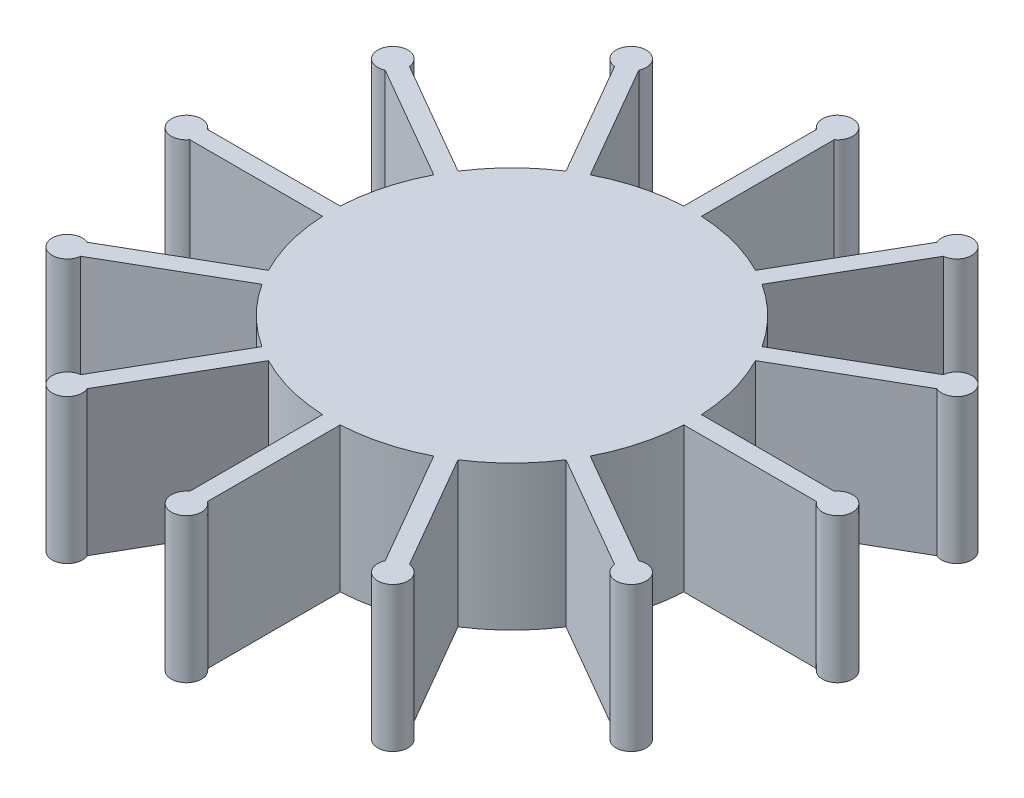
SolidWorks part; units mm, degrees
ref_plane "Front Plane" through (0, 0, 0) normal (0, 0, 1) x (1, 0, 0)
ref_plane "Top Plane" through (0, 0, 0) normal (0, 1, 0) x (1, 0, 0)
ref_plane "Right Plane" through (0, 0, 0) normal (1, 0, 0) x (0, 0, -1)
sketch "Sketch1" plane through (0, 0, 0) normal (0, 1, 0) x (1, 0, 0)
  line L9 (-0.7358, 25.9895) -> (-0.7358, 14.9819)
  line L10 (0.7358, 25.9895) -> (0.7358, 14.9819)
  line L11 (12.3575, 22.8755) -> (6.8537, 13.3427)
  line L12 (13.632, 22.1397) -> (8.1282, 12.6068)
  line L13 (22.1397, 13.632) -> (12.6068, 8.1282)
  line L14 (22.8755, 12.3575) -> (13.3427, 6.8537)
  line L15 (25.9895, 0.7358) -> (14.9819, 0.7358)
  line L16 (25.9895, -0.7358) -> (14.9819, -0.7358)
  line L17 (22.8755, -12.3575) -> (13.3427, -6.8537)
  line L18 (22.1397, -13.632) -> (12.6068, -8.1282)
  line L19 (13.632, -22.1397) -> (8.1282, -12.6068)
  line L20 (12.3575, -22.8755) -> (6.8537, -13.3427)
  line L21 (0.7358, -25.9895) -> (0.7358, -14.9819)
  line L22 (-0.7358, -25.9895) -> (-0.7358, -14.9819)
  line L23 (-12.3575, -22.8755) -> (-6.8537, -13.3427)
  line L24 (-13.632, -22.1397) -> (-8.1282, -12.6068)
  line L25 (-22.1397, -13.632) -> (-12.6068, -8.1282)
  line L26 (-22.8755, -12.3575) -> (-13.3427, -6.8537)
  line L27 (-25.9895, -0.7358) -> (-14.9819, -0.7358)
  line L28 (-25.9895, 0.7358) -> (-14.9819, 0.7358)
  line L29 (-22.8755, 12.3575) -> (-13.3427, 6.8537)
  line L30 (-22.1397, 13.632) -> (-12.6068, 8.1282)
  line L31 (-13.632, 22.1397) -> (-8.1282, 12.6068)
  line L32 (-12.3575, 22.8755) -> (-6.8537, 13.3427)
  arc A8 (6.8537, 13.3427) -> (0.7358, 14.9819) centre (0, 0) ccw
  arc A9 (0.7358, 25.9895) -> (-0.7358, 25.9895) centre (0, 27) ccw
  arc A10 (13.632, 22.1397) -> (12.3575, 22.8755) centre (13.5, 23.3827) ccw
  arc A11 (22.8755, 12.3575) -> (22.1397, 13.632) centre (23.3827, 13.5) ccw
  arc A12 (25.9895, -0.7358) -> (25.9895, 0.7358) centre (27, 0) ccw
  arc A13 (22.1397, -13.632) -> (22.8755, -12.3575) centre (23.3827, -13.5) ccw
  arc A14 (12.3575, -22.8755) -> (13.632, -22.1397) centre (13.5, -23.3827) ccw
  arc A15 (-0.7358, -25.9895) -> (0.7358, -25.9895) centre (0, -27) ccw
  arc A16 (-13.632, -22.1397) -> (-12.3575, -22.8755) centre (-13.5, -23.3827) ccw
  arc A17 (-22.8755, -12.3575) -> (-22.1397, -13.632) centre (-23.3827, -13.5) ccw
  arc A18 (-25.9895, 0.7358) -> (-25.9895, -0.7358) centre (-27, 0) ccw
  arc A19 (-22.1397, 13.632) -> (-22.8755, 12.3575) centre (-23.3827, 13.5) ccw
  arc A20 (-12.3575, 22.8755) -> (-13.632, 22.1397) centre (-13.5, 23.3827) ccw
  arc A21 (12.6068, 8.1282) -> (8.1282, 12.6068) centre (0, 0) ccw
  arc A22 (14.9819, 0.7358) -> (13.3427, 6.8537) centre (0, 0) ccw
  arc A23 (-8.1282, 12.6068) -> (-12.6068, 8.1282) centre (0, 0) ccw
  arc A24 (-13.3427, 6.8537) -> (-14.9819, 0.7358) centre (0, 0) ccw
  arc A25 (-14.9819, -0.7358) -> (-13.3427, -6.8537) centre (0, 0) ccw
  arc A26 (-12.6068, -8.1282) -> (-8.1282, -12.6068) centre (0, 0) ccw
  arc A27 (-6.8537, -13.3427) -> (-0.7358, -14.9819) centre (0, 0) ccw
  arc A28 (0.7358, -14.9819) -> (6.8537, -13.3427) centre (0, 0) ccw
  arc A29 (8.1282, -12.6068) -> (12.6068, -8.1282) centre (0, 0) ccw
  arc A30 (13.3427, -6.8537) -> (14.9819, -0.7358) centre (0, 0) ccw
  arc A31 (-0.7358, 14.9819) -> (-6.8537, 13.3427) centre (0, 0) ccw
  point P53 (0, 0)
  point P68 (0, 0)
  dimension "D2" = 12
  dimension "D4" = 8
extrude "Boss-Extrude1" add sketch "Sketch1" along normal blind 12
